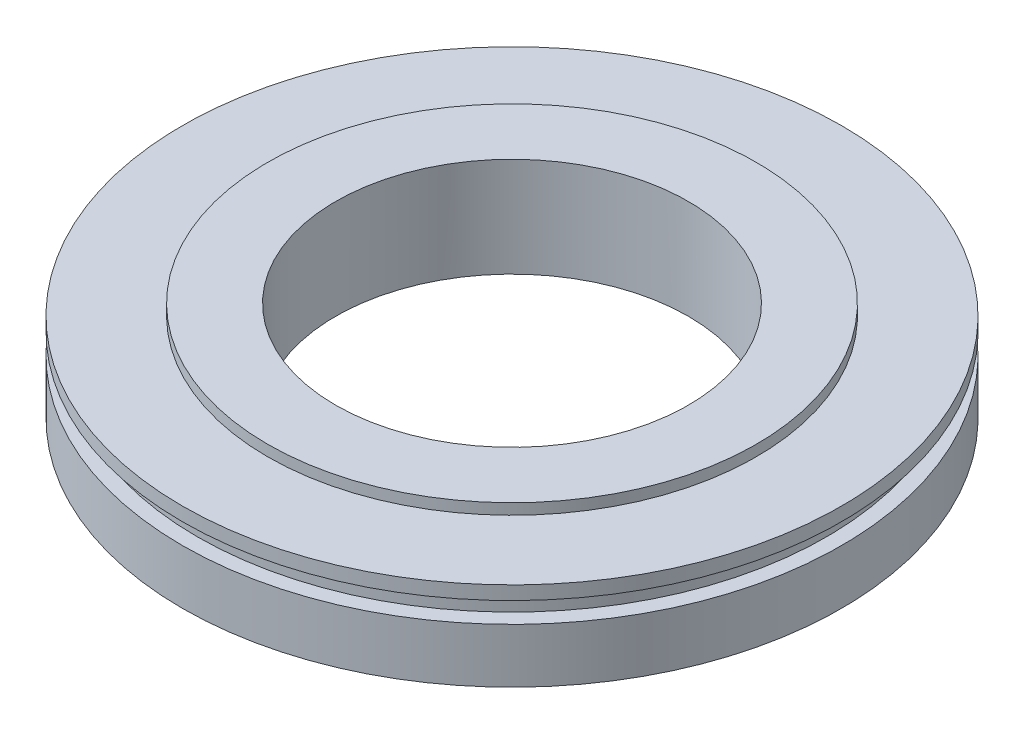
SolidWorks part; units mm, degrees
material "6061-T6 (SS)"
ref_plane "X-Y Datum" through (0, 0, 0) normal (0, 0, 1) x (1, 0, 0)
ref_plane "X-Z Datum" through (0, 0, 0) normal (0, 1, 0) x (1, 0, 0)
ref_plane "Y-Z Datum" through (0, 0, 0) normal (1, 0, 0) x (0, 0, -1)
sketch "Sketch1" plane through (0, 0, 0) normal (1, 0, 0) x (0, 0, -1)
  line L0 (-16.51, 2.6941) -> (-16.51, -5.0208)
  line L1 (-16.51, -5.0208) -> (-30.8407, -5.0208)
  line L4 (-29.4348, -0.5063) -> (-29.4348, 1.4241)
  line L7 (-30.8407, 2.6941) -> (-16.51, 2.6941)
  line L8 (0, 0) -> (0, -47872.0541) construction
  line L9 (0, 0) -> (-47872.0541, 0) construction
  line L10 (-30.8407, -0.5063) -> (-30.8407, -5.0208)
  line L11 (-14.7421, 2.6941) -> (15.0495, 2.6941) construction
  line L12 (-30.9994, 12.7) -> (-30.9994, -12.7) construction
  line L13 (14.2875, -5.0208) -> (-14.2875, -5.0208) construction
  line L15 (-30.8407, 2.6941) -> (-30.8407, 1.4241)
  line L16 (-30.8407, 1.4241) -> (-29.4348, 1.4241)
  line L17 (-29.4348, -0.5063) -> (-30.8407, -0.5063)
  point P15 (-30.9994, 0)
  dimension "D3" = 1.27
  dimension "D1" = 33.02
  dimension "D2" = 61.6814
  dimension "D4" = 1.9304
  dimension "D5" = 25.4
  dimension "D6" = 61.9989
  dimension "D7" = 1.5646
revolve "Revolve1" add sketch "Sketch1" angle 360 about L8
ref_plane "Plane1" through (0, 1.4241, 0) normal (0, 1, 0) x (1, 0, 0)
sketch "Sketch3" plane through (0, 2.6941, 0) normal (0, 1, 0) x (1, 0, 0)
  circle A0 centre (0, 0) radius 30.8407
  circle A1 centre (0, 0) radius 16.51
  circle A2 centre (0, 0) radius 16.51 construction
  circle A4 centre (0, 0) radius 30.8407 construction
extrude "BandAid Solution thicker" add sketch "Sketch3" along normal up to surface (-1.27 mm away) up to plane "Plane1"
sketch "Sketch4" plane through (0, 2.6941, 0) normal (0, 1, 0) x (1, 0, 0)
  circle A0 centre (0, 0) radius 16.51
  circle A1 centre (0, 0) radius 22.86
  circle A3 centre (0, 0) radius 16.51 construction
  dimension "D1" = 45.72
extrude "Lip for Bearing" add sketch "Sketch4" along normal blind 1.016
sketch "Sketch5" plane through (0, -5.0208, 0) normal (0, -1, 0) x (1, 0, 0)
  circle A3 centre (0, 0) radius 16.51
  circle A4 centre (0, 0) radius 30.8407
  circle A5 centre (0, 0) radius 30.8407 construction
  circle A6 centre (0, 0) radius 16.51 construction
extrude "Boss-Extrude1" add sketch "Sketch5" along normal blind 0.5791
move or copy body "Body-Move/Copy1" [suppressed] bodies to move or copy 105 parameters "D1"=0, "D2"=0, "D3"=0
